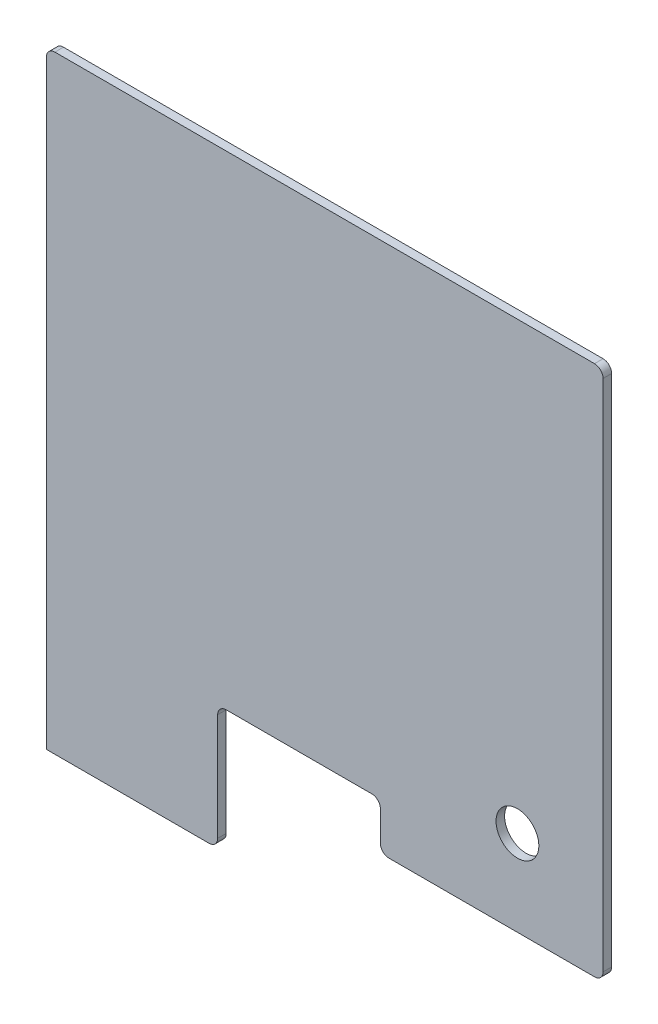
SolidWorks part; units mm, degrees
ref_plane "Front Plane" through (0, 0, 0) normal (0, 0, 1) x (1, 0, 0)
ref_plane "Top Plane" through (0, 0, 0) normal (0, 1, 0) x (1, 0, 0)
ref_plane "Right Plane" through (0, 0, 0) normal (1, 0, 0) x (0, 0, -1)
sketch "Sketch2" plane through (0, 0, 0) normal (0, 0, 1) x (1, 0, 0)
  line L0 (0, 0) -> (-165.1, 0)
  line L1 (-285.75, 34.925) -> (-285.75, -57.15)
  line L2 (-285.75, -57.15) -> (-412.75, -57.15)
  line L3 (-412.75, -57.15) -> (-412.75, 393.7)
  line L4 (-412.75, 393.7) -> (0, 393.7)
  line L5 (0, 393.7) -> (0, 0)
  line L6 (-165.1, 0) -> (-165.1, 34.925)
  line L7 (-165.1, 34.925) -> (-285.75, 34.925)
  circle A0 centre (-63.5, 63.5) radius 15.875
  point P1 (0, 0)
  point P11 (0, 0)
  point P13 (-247.65, 72.781)
  dimension "D1" = 31.75
  dimension "D2" = 349.25
  dimension "D3" = 330.2
  dimension "D4" = 63.5
  dimension "D5" = 127
  dimension "D6" = 120.65
  dimension "D7" = 120.65
  dimension "D8" = 63.5
  dimension "D9" = 92.075
extrude "Boss-Extrude1" add sketch "Sketch2" along normal blind 6.35
fillet "Fillet1" radius 6.35 7 edges at (-412.75, 393.7, 3.175) (0, 393.7, 3.175) (0, 0, 3.175) (-165.1, 0, 3.175) (-165.1, 34.925, 3.175) (-285.75, 34.925, 3.175) (-285.75, -57.15, 3.175)
